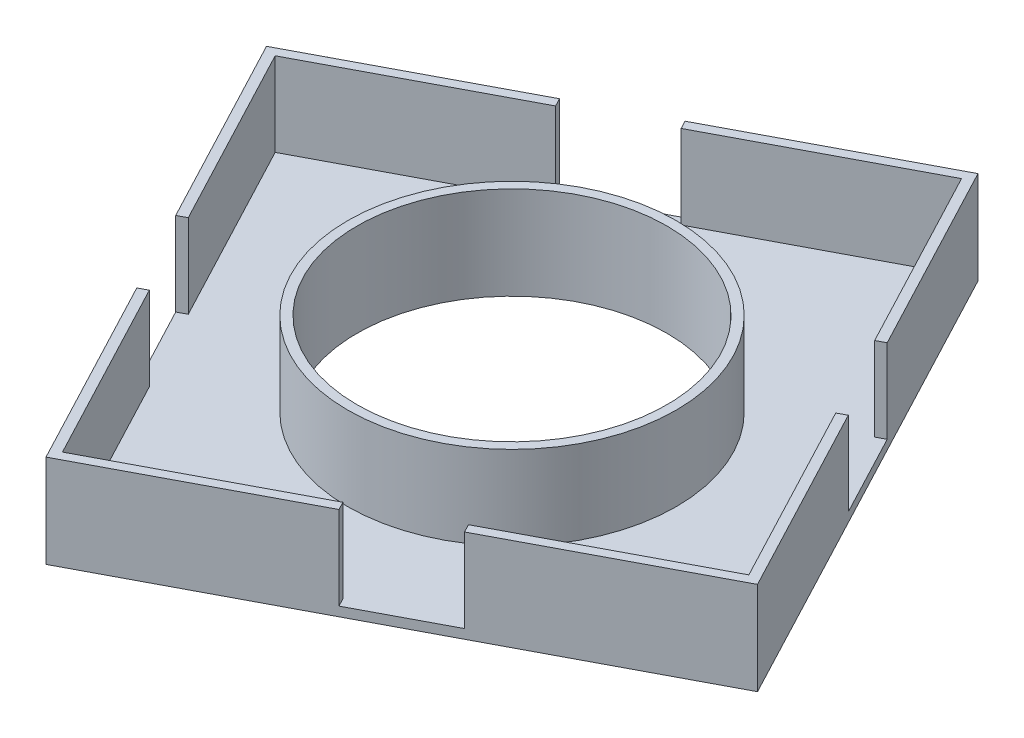
SolidWorks part; units mm, degrees
ref_plane "Front Plane" through (0, 0, 0) normal (0, 0, 1) x (1, 0, 0)
ref_plane "Top Plane" through (0, 0, 0) normal (0, 1, 0) x (1, 0, 0)
ref_plane "Right Plane" through (0, 0, 0) normal (1, 0, 0) x (0, 0, -1)
sketch "Sketch2" plane through (0, 0, 0) normal (0, 1, 0) x (1, 0, 0)
  line L1 (-35.583, -114.8209) -> (114.8209, -35.583)
  line L2 (114.8209, -35.583) -> (35.583, 114.8209)
  line L3 (35.583, 114.8209) -> (-114.8209, 35.583)
  line L4 (-114.8209, 35.583) -> (-35.583, -114.8209)
  circle A0 centre (0, 0) radius 50
  circle A1 centre (0, 0) radius 85 construction
extrude "Boss-Extrude1" add sketch "Sketch2" along normal blind 30 contours L3 L4 L1 L2 | A0
sketch "Sketch6" plane through (0, 0, 0) normal (0, -1, 0) x (-1, 0, 0)
  line L0 (114.8209, 35.583) -> (47.7592, 14.8006)
  circle A0 centre (0, 0) radius 50 construction
  circle A1 centre (76.4147, 23.6809) radius 2
  circle A2 centre (23.6809, -76.4147) radius 2
  circle A3 centre (-76.4147, -23.6809) radius 2
  circle A4 centre (-23.6809, 76.4147) radius 2
  point P16 (0, 0)
  dimension "D1" = 30
  dimension "D2" = 4
extrude "Boss-Extrude5" add sketch "Sketch6" along normal blind 20 contours A1 | A4 | A3 | A2
fillet "Fillet2" radius 2 8 edges at (-23.6809, 0, 78.4147) (-23.6809, -20, 74.4147) (76.4147, 0, 25.6809) (76.4147, -20, 21.6809) (-76.4147, 0, -21.6809) (-76.4147, -20, -25.6809) (23.6809, 0, -74.4147) (23.6809, -20, -78.4147)
shell "Shell1" thickness 3 removed face at (0, 30, 0)
sketch "Sketch7" plane through (0, 30, 0) normal (0, 1, 0) x (1, 0, 0)
  line L1 (79.5394, 24.9497) -> (82.1936, 26.348)
  line L2 (110.7684, -34.3271) -> (34.3271, 110.7684) construction
  line L3 (114.8209, -35.583) -> (35.583, 114.8209) construction
  line L4 (82.1936, 26.348) -> (68.2104, 52.8899)
  line L5 (68.2104, 52.8899) -> (65.5562, 51.4916)
  line L6 (65.5562, 51.4916) -> (79.5394, 24.9497)
  line L7 (51.4916, -65.5562) -> (24.9497, -79.5394)
  line L8 (24.9497, -79.5394) -> (26.348, -82.1936)
  line L9 (26.348, -82.1936) -> (52.8899, -68.2104)
  line L10 (52.8899, -68.2104) -> (51.4916, -65.5562)
  line L11 (-65.5562, -51.4916) -> (-79.5394, -24.9497)
  line L12 (-79.5394, -24.9497) -> (-82.1936, -26.348)
  line L13 (-82.1936, -26.348) -> (-68.2104, -52.8899)
  line L14 (-68.2104, -52.8899) -> (-65.5562, -51.4916)
  line L15 (-51.4916, 65.5562) -> (-24.9497, 79.5394)
  line L16 (-24.9497, 79.5394) -> (-26.348, 82.1936)
  line L17 (-26.348, 82.1936) -> (-52.8899, 68.2104)
  line L18 (-52.8899, 68.2104) -> (-51.4916, 65.5562)
  point P9 (75.202, 39.619)
  point P10 (75.202, 39.619)
  point P25 (0, 0)
  dimension "D1" = 30
  dimension "D2" = 15
  dimension "D3" = 4
extrude "Cut-Extrude3" cut sketch "Sketch7" against normal blind 27
